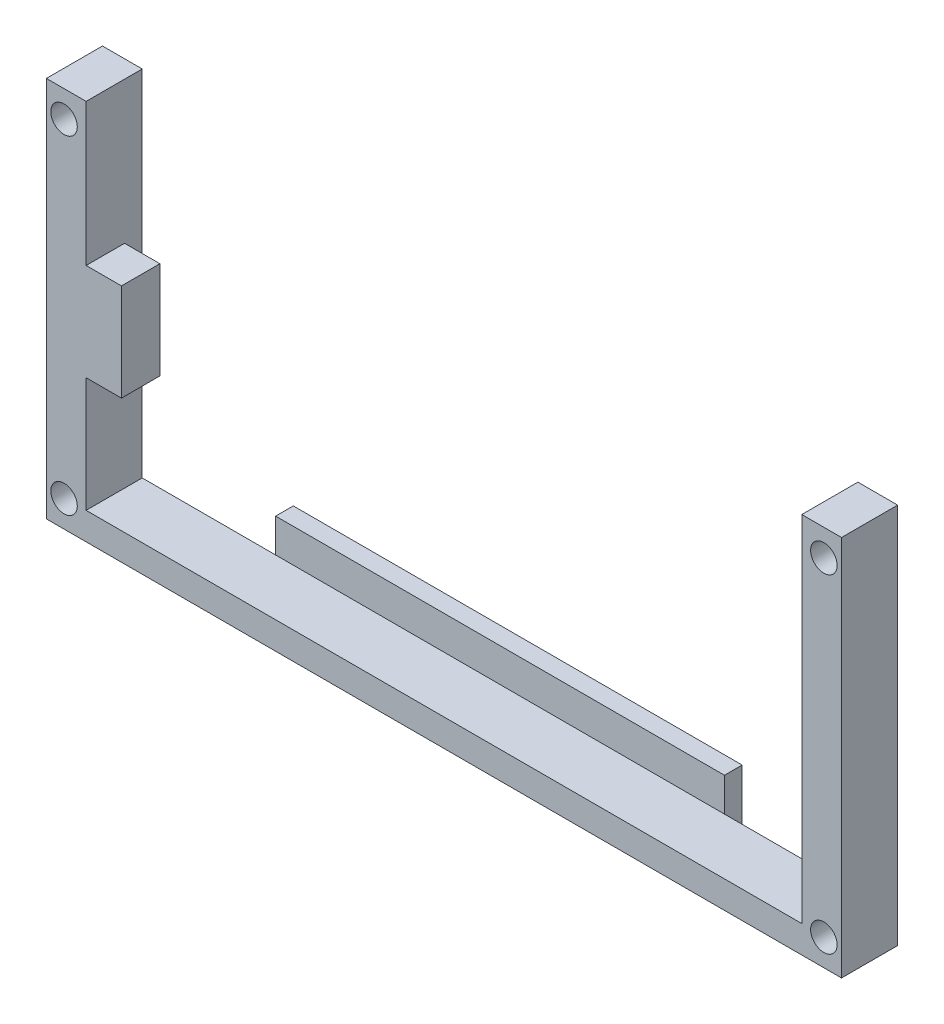
SolidWorks part; units mm, degrees
ref_plane "Front Plane" through (0, 0, 0) normal (0, 0, 1) x (1, 0, 0)
ref_plane "Top Plane" through (0, 0, 0) normal (0, 1, 0) x (1, 0, 0)
ref_plane "Right Plane" through (0, 0, 0) normal (1, 0, 0) x (0, 0, -1)
sketch "Sketch1" plane through (0, 0, 0) normal (0, 0, 1) x (1, 0, 0)
  line L1 (-45, 21.59) -> (45, 21.59)
  line L2 (-45, 21.59) -> (-45, -21.59)
  line L3 (-45, -21.59) -> (45, -21.59)
  line L4 (45, 21.59) -> (45, -21.59)
  line L5 (-40.5, 18.5) -> (40.5, 18.5)
  line L6 (-40.5, 18.5) -> (-40.5, -18.5)
  line L7 (-40.5, -18.5) -> (40.5, -18.5)
  line L8 (40.5, 18.5) -> (40.5, -18.5)
  point P4 (0, 21.59)
  point P5 (-45, 0)
  point P11 (0, 18.5)
  point P12 (-40.5, 0)
  dimension "D1" = 90
  dimension "D2" = 43.18
  dimension "D3" = 81
  dimension "D4" = 37
extrude "Boss-Extrude1" add sketch "Sketch1" along normal blind 6.35
sketch "Sketch2" plane through (0, 0, 6.35) normal (0, 0, 1) x (1, 0, 0)
  line L0 (45, -21.59) -> (45, 21.59) construction
  line L1 (45, 21.59) -> (-45, 21.59) construction
  line L2 (0, -55) -> (0, 55) construction
  line L4 (55, 0) -> (-55, 0) construction
  circle A1 centre (43, 18.59) radius 1.5
  circle A2 centre (-43, 18.59) radius 1.5
  circle A3 centre (-43, -18.59) radius 1.5
  circle A4 centre (43, -18.59) radius 1.5
  dimension "D1" = 2
  dimension "D3" = 3
  dimension "D2" = 3
extrude "Cut-Extrude1" cut sketch "Sketch2" against normal blind 10.16
sketch "Sketch4" plane through (-40.5, 0, 0) normal (1, 0, 0) x (0, 0, -1)
  line L0 (-6.35, -21.59) -> (-6.35, 21.59) construction
  line L1 (-6.35, 5.5) -> (-2, 5.5)
  line L2 (-6.35, 5.5) -> (-6.35, -5.5)
  line L3 (-6.35, -5.5) -> (-2, -5.5)
  line L4 (-2, 5.5) -> (-2, -5.5)
  point P6 (-2, 0)
  dimension "D1" = 11
  dimension "D2" = 4.35
extrude "Boss-Extrude3" add sketch "Sketch4" along normal blind 4
sketch "Sketch5" plane through (0, 0, 0) normal (0, 0, -1) x (-1, 0, 0)
  line L0 (-45, 21.59) -> (45, 21.59) construction
  line L1 (-40.5, 21.59) -> (40.5, 21.59)
  line L2 (-40.5, 21.59) -> (-40.5, 18.5)
  line L3 (-40.5, 18.5) -> (40.5, 18.5)
  line L4 (40.5, 21.59) -> (40.5, 18.5)
  point P7 (-40.5, 18.5)
extrude "Cut-Extrude2" cut sketch "Sketch5" against normal through all
sketch "Sketch6" plane through (0, 0, 0) normal (0, 0, -1) x (-1, 0, 0)
  line L0 (40.5, -18.5) -> (-40.5, -18.5) construction
  line L1 (-25.4, -18.5) -> (25.4, -18.5)
  line L2 (-25.4, -18.5) -> (-25.4, -21.59)
  line L3 (-25.4, -21.59) -> (25.4, -21.59)
  line L4 (25.4, -18.5) -> (25.4, -21.59)
  line L5 (45, -21.59) -> (-45, -21.59) construction
  point P8 (0, -18.5)
  dimension "D1" = 50.8
extrude "Boss-Extrude4" add sketch "Sketch6" along normal blind 2
sketch "Sketch7" plane through (0, -18.5, 0) normal (0, 1, 0) x (1, 0, 0)
  line L1 (-25.4, 2) -> (25.4, 2)
  line L2 (-25.4, 2) -> (-25.4, 0)
  line L3 (-25.4, 0) -> (25.4, 0)
  line L4 (25.4, 2) -> (25.4, 0)
extrude "Boss-Extrude5" add sketch "Sketch7" along normal blind 3.81
